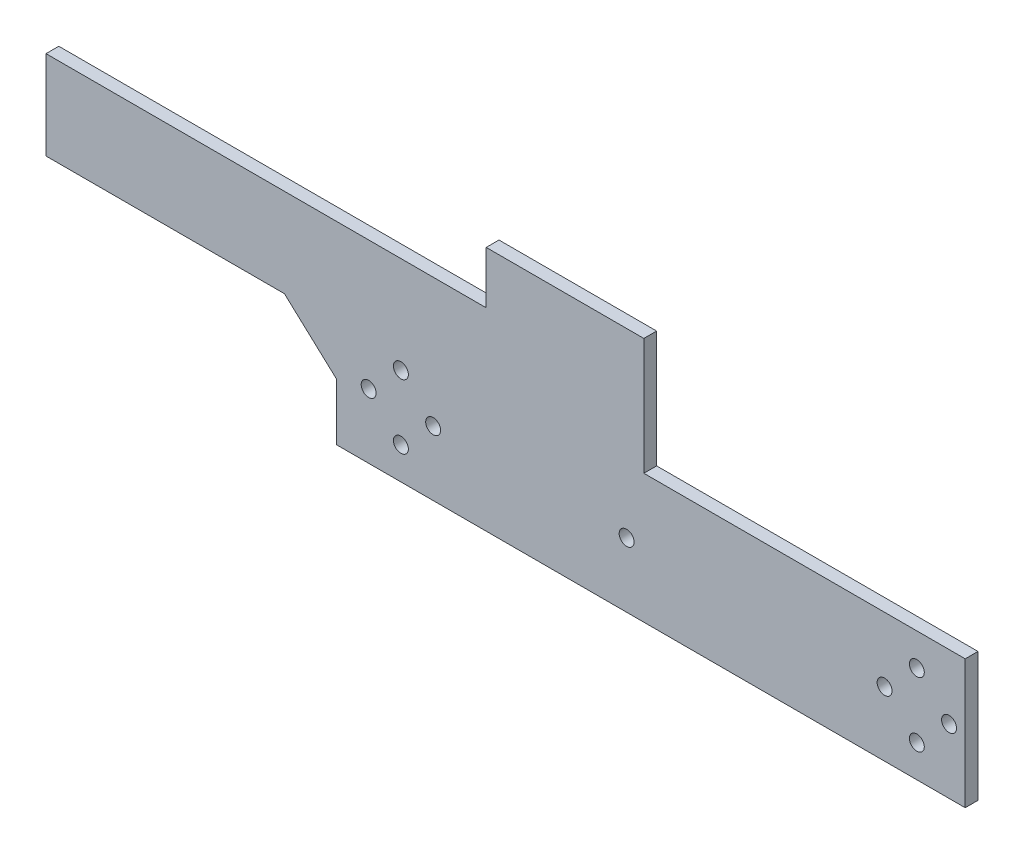
SolidWorks part; units mm, degrees
ref_plane "Front" through (0, 0, 0) normal (0, 0, 1) x (1, 0, 0)
ref_plane "Top" through (0, 0, 0) normal (0, 1, 0) x (1, 0, 0)
ref_plane "Right" through (0, 0, 0) normal (1, 0, 0) x (0, 0, -1)
ref_axis "side-side" through (80.9, 0, 0) along (-1, 0, 0)
ref_axis "up-down" through (0, 50, 0) along (0, -1, 0)
ref_axis "front-back" through (0, 0, -80.9) along (0, 0, 1)
sketch "Sketch1" plane through (0, 0, 0) normal (0, 0, 1) x (1, 0, 0)
  line L0 (288, 0) -> (0, 0) construction
  line L1 (156, 0) -> (0, 0)
  line L2 (0, 29.5) -> (0, 2.5) construction
  line L3 (0, 14.15) -> (0, 0)
  line L4 (-12.8974, 26) -> (-72.0466, 26)
  line L6 (-49.8578, 108.2) -> (-49.8578, 26) construction
  line L7 (0, 14.15) -> (-12.8974, 26)
  line L9 (-72.0466, 48) -> (37.159, 48)
  line L11 (-72.0466, 30.4974) -> (-72.0466, 280.05) construction
  line L12 (-72.0466, 26) -> (-72.0466, 48)
  line L13 (76.2722, 60.975) -> (37.159, 60.975) construction
  line L14 (76.2722, 60.975) -> (37.159, 60.975)
  line L16 (76.2722, 60.975) -> (76.2722, 32)
  line L17 (37.159, 102.2) -> (37.159, 3.2) construction
  line L18 (37.159, 60.975) -> (37.159, 48)
  line L19 (285.5, 32) -> (2.5, 32) construction
  line L20 (76.2722, 32) -> (156, 32)
  line L21 (156, 32) -> (156, 0)
  circle A0 centre (144, 8) radius 1.85 construction
  circle A1 centre (144, 24) radius 1.85 construction
  circle A2 centre (152, 16) radius 1.85 construction
  circle A3 centre (136, 16) radius 1.85 construction
  circle A4 centre (144, 8) radius 1.85
  circle A5 centre (144, 24) radius 1.85
  circle A6 centre (152, 16) radius 1.85
  circle A7 centre (136, 16) radius 1.85
  circle A8 centre (24, 16) radius 1.85 construction
  circle A9 centre (16, 8) radius 1.85 construction
  circle A10 centre (8, 16) radius 1.85 construction
  circle A11 centre (16, 24) radius 1.85 construction
  circle A12 centre (24, 16) radius 1.85
  circle A13 centre (16, 8) radius 1.85
  circle A14 centre (8, 16) radius 1.85
  circle A15 centre (16, 24) radius 1.85
  circle A16 centre (72, 16) radius 1.85 construction
  circle A17 centre (72, 16) radius 1.85
  dimension "D1" = 26
  dimension "D2" = 48
  dimension "D3" = 156
extrude "Boss-Extrude1" add sketch "Sketch1" along normal blind 3.175
